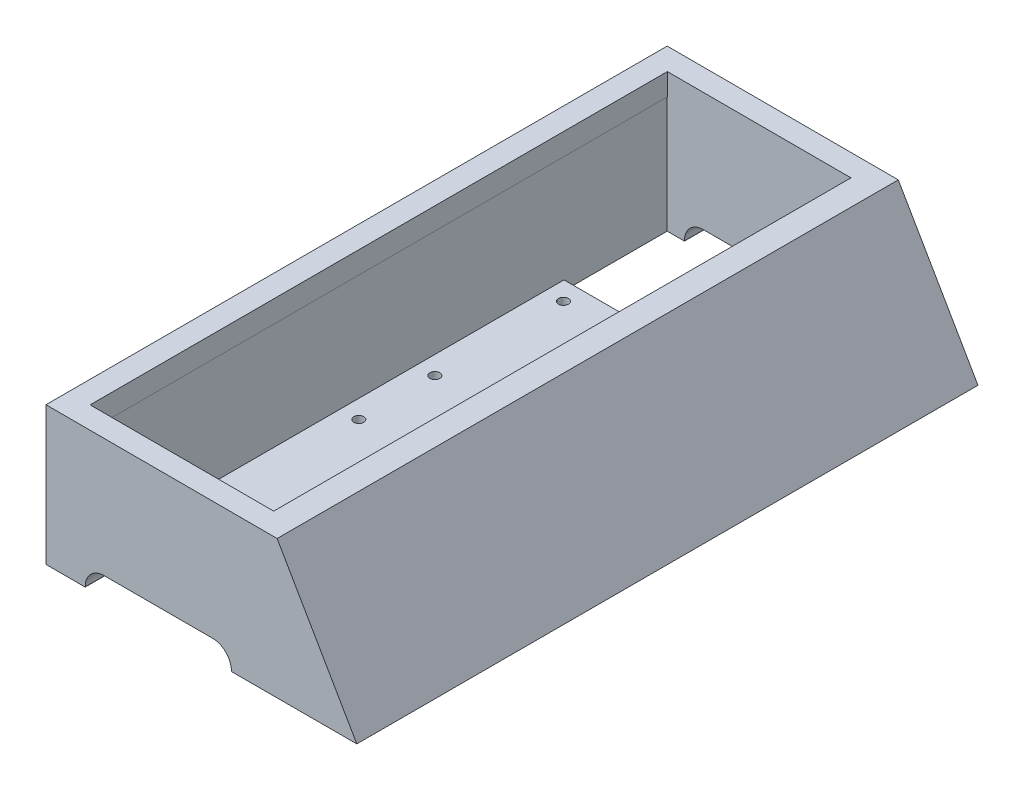
SolidWorks part; units mm, degrees
ref_plane "Alzado" through (0, 0, 0) normal (0, 0, 1) x (1, 0, 0)
ref_plane "Planta" through (0, 0, 0) normal (0, 1, 0) x (1, 0, 0)
ref_plane "Vista lateral" through (0, 0, 0) normal (1, 0, 0) x (0, 0, -1)
sketch "Sketch1" plane through (0, 0, 0) normal (0, 0, 1) x (1, 0, 0)
  line L0 (0, 0) -> (99.07, 0)
  line L1 (99.07, 0) -> (73.665, 44.0028)
  line L2 (0, 0) -> (0, 44.1)
  line L3 (0, 44.1) -> (73.665, 44.0028)
  dimension "D1" = 99.07
  dimension "D2" = 60
  dimension "D3" = 50.81
  dimension "D4" = 44.1
  dimension "D5" = 90
extrude "Boss-Extrude1" add sketch "Sketch1" along normal blind 198
shell "Shell1" thickness 7 removed face at (49.535, 0, 99)
sketch "Sketch2" plane through (68.2403, 39.3986, 0) normal (-0.866, -0.5, 0) x (0, 0, 1)
  line L0 (191, -3.5) -> (191, -45.4935) construction
  line L1 (7, -45.4935) -> (191, -45.4935)
  line L2 (7, -45.4935) -> (7, 46.3403)
  line L3 (7, 46.3403) -> (191, 46.3403)
  line L4 (191, -45.4935) -> (191, 46.3403)
  line L5 (7, -45.4935) -> (7, -2.7603) construction
  dimension "D1" = 0
  dimension "D2" = 0
extrude "Cut-Extrude1" cut sketch "Sketch2" along normal blind 10
sketch "Sketch3" plane through (0.0582, 44.0999, 0) normal (0.0013, 1, 0) x (1, -0.0013, 0)
  line L0 (7, -7) -> (90.987, -7) construction
  line L1 (7, -191) -> (58.0157, -191)
  line L2 (7, -191) -> (7, -7)
  line L3 (7, -7) -> (58.0157, -7)
  line L4 (58.0157, -191) -> (58.0157, -7)
  line L5 (7, -191) -> (90.987, -191) construction
  line L6 (7, -191) -> (7, -7) construction
  line L7 (58.0157, -7) -> (58.0157, -191) construction
  dimension "D1" = 0
  dimension "D2" = 0
  dimension "D3" = 0
  dimension "D4" = 0
extrude "Cut-Extrude3" cut sketch "Sketch3" against normal blind 10
sketch "Sketch4" plane through (0, 0, 0) normal (0, -1, 0) x (1, 0, 0)
  line L0 (7, 191) -> (7, 158.11) construction
  line L1 (7.049, 7) -> (7.049, 39.89) construction
  line L2 (90.9871, 191) -> (90.9871, 7) construction
  line L3 (7, 158.11) -> (50.2271, 158.11)
  line L4 (7, 158.11) -> (7, 39.89)
  line L5 (7, 39.89) -> (50.2271, 39.89)
  line L6 (50.2271, 158.11) -> (50.2271, 39.89)
  line L7 (7, 191) -> (90.9871, 191) construction
  line L8 (7, 7) -> (90.9871, 7) construction
  line L9 (74.5927, 40.95) -> (74.5927, 7) construction
  line L10 (74.5927, 157.05) -> (74.5927, 191) construction
  line L11 (84.5927, 191) -> (74.5927, 191)
  line L12 (84.5927, 191) -> (84.5927, 181)
  line L13 (84.5927, 181) -> (74.5927, 181)
  line L14 (74.5927, 191) -> (74.5927, 181)
  line L15 (84.5927, 7) -> (74.5927, 7)
  line L16 (84.5927, 7) -> (84.5927, 17)
  line L17 (84.5927, 17) -> (74.5927, 17)
  line L18 (74.5927, 7) -> (74.5927, 17)
  dimension "D1" = 32.89
  dimension "D2" = 32.89
  dimension "D3" = 40.76
  dimension "D4" = 32.89
  dimension "D5" = 32.89
  dimension "D6" = 10
  dimension "D7" = 10
  dimension "D8" = 10
  dimension "D9" = 10
extrude "Boss-Extrude2" add sketch "Sketch4" against normal blind 3
sketch "Sketch6" plane through (0, 3, 0) normal (0, 1, 0) x (1, 0, 0)
  circle A0 centre (12.8305, -45.8872) radius 1.585
  circle A1 centre (12.8305, -86.8872) radius 1.585
  circle A2 centre (12.8305, -111.1128) radius 1.585
  circle A3 centre (12.8305, -152.1128) radius 1.585
extrude "Cut-Extrude5" cut sketch "Sketch6" against normal blind 10
sketch "Sketch8" plane through (0, 0, 0) normal (0, -1, 0) x (-1, 0, 0)
  circle A0 centre (-79.5927, -186) radius 1.585
  circle A1 centre (-79.5927, -12) radius 1.585
extrude "Cut-Extrude6" cut sketch "Sketch8" against normal blind 10
sketch "Sketch9" plane through (0, 0, 198) normal (0, 0, 1) x (1, 0, 0)
  line L0 (0, 44.1) -> (0, 0) construction
  line L1 (12.5, 0) -> (59.0927, 0)
  line L2 (12.5, 0) -> (12.5, 6.1795)
  line L3 (12.5, 6.1795) -> (59.0927, 6.1795)
  line L4 (59.0927, 0) -> (59.0927, 6.1795)
  line L5 (71.5927, -45.1936) -> (71.5927, 0) construction
  dimension "D1" = 12.5
  dimension "D2" = 12.5
extrude "Cut-Extrude7" cut sketch "Sketch9" against normal blind 10
ref_plane "Plane1" through (0, 0, 99) normal (0, 0, -1) x (-1, 0, 0)
mirror "Mirror1" about plane through (0, 0, 99) normal (0, 0, -1) of "Cut-Extrude7"
fillet "Fillet1" radius 6 2 edges at (12.5, 6.1795, 3.5) (59.0927, 6.1795, 3.5)
fillet "Fillet2" radius 6 2 edges at (59.0927, 6.1795, 194.5) (12.5, 6.1795, 194.5)
